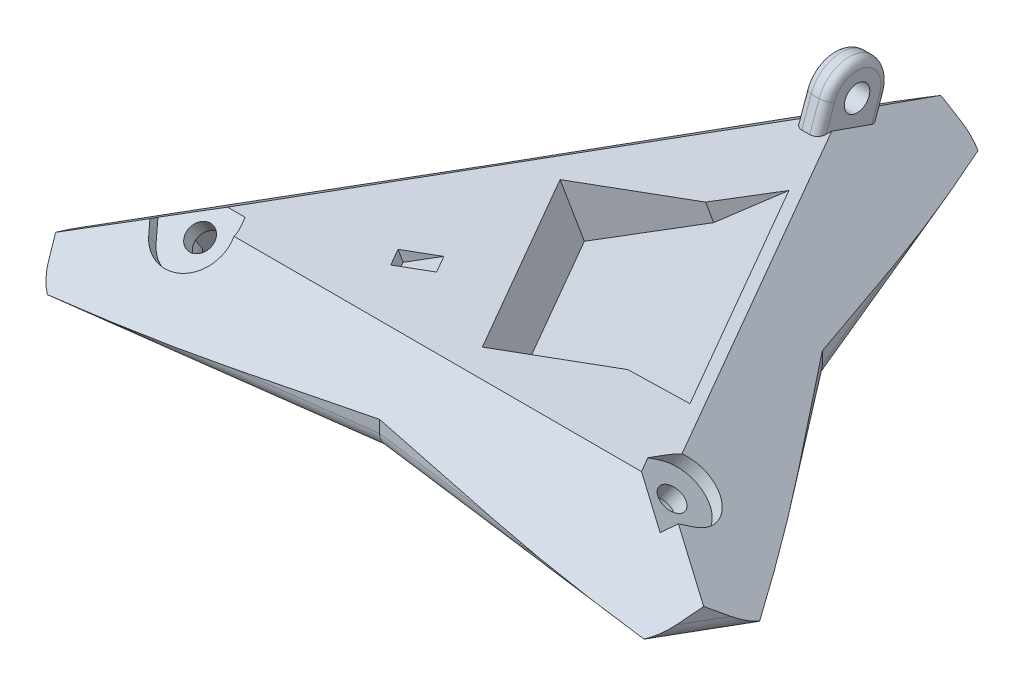
SolidWorks part; units mm, degrees
ref_plane "Front Plane" through (0, 0, 0) normal (0, 0, 1) x (1, 0, 0)
ref_plane "Top Plane" through (0, 0, 0) normal (0, 1, 0) x (1, 0, 0)
ref_plane "Right Plane" through (0, 0, 0) normal (1, 0, 0) x (0, 0, -1)
sketch "Sketch2" plane through (0, 0, 0) normal (0, 1, 0) x (1, 0, 0)
  line L0 (0, 57.735) -> (-50, -28.8675)
  line L1 (-50, -28.8675) -> (50, -28.8675)
  line L2 (50, -28.8675) -> (0, 57.735)
  line L3 (0, 0) -> (0, 57.735) construction
  line L4 (50, -28.8675) -> (0, 0) construction
  line L5 (0, 0) -> (-50, -28.8675) construction
  line L6 (0, 0) -> (0, -28.8675) construction
  line L7 (0, 0) -> (25, 14.4338) construction
  line L8 (0, 0) -> (-25, 14.4338) construction
  line L9 (10, 40.4145) -> (0, 34.641) construction
  line L10 (0, 34.641) -> (-10, 40.4145) construction
  dimension "D1" = 20
sketch "Sketch3" plane through (0, 0, 0) normal (1, 0, 0) x (0, 0, -1)
  line L0 (-28.8675, 0) -> (-19.245, 27.2166) construction
  line L1 (-19.245, 27.2166) -> (0, 20.4124) construction
  line L2 (0, 20.4124) -> (-28.8675, 0) construction
  line L3 (-19.245, 27.2166) -> (-28.983, -0.3266) construction
  line L4 (-28.983, -0.3266) -> (0.2309, 20.3308)
  line L5 (0.2309, 20.3308) -> (-19.245, 27.2166)
  line L6 (-28.983, -0.3266) -> (-28.983, 27.2166)
  line L7 (-28.983, 27.2166) -> (-19.245, 27.2166)
  line L8 (0, 0) -> (0, 103.8474) construction
  dimension "D1" = 0.2
ref_plane "Plane1" through (0, 0, 0) normal (0.5, 0, 0.866) x (0.866, 0, -0.5)
sketch "Sketch4" plane through (0, 0, 0) normal (0.5, 0, 0.866) x (0.866, 0, -0.5)
  line L0 (0, 20.4124) -> (19.245, 27.2166) construction
  line L1 (19.245, 27.2166) -> (28.8675, 0) construction
  line L2 (28.8675, 0) -> (0, 20.4124) construction
  line L3 (0, 81.6497) -> (0, 0) construction
  line L4 (-0.2309, 20.3308) -> (19.245, 27.2166)
  line L5 (19.245, 27.2166) -> (28.983, -0.3266) construction
  line L6 (28.983, -0.3266) -> (-0.2309, 20.3308)
  line L7 (19.245, 27.2166) -> (28.983, 27.2166)
  line L8 (28.983, 27.2166) -> (28.983, -0.3266)
  dimension "D1" = 0.2
ref_plane "Plane2" through (0, 0, 0) normal (0.5, 0, -0.866) x (-0.866, 0, -0.5)
sketch "Sketch5" plane through (0, 0, 0) normal (0.5, 0, -0.866) x (-0.866, 0, -0.5)
  line L0 (19.245, 27.2166) -> (0, 20.4124) construction
  line L1 (0, 20.4124) -> (28.8675, 0) construction
  line L2 (28.8675, 0) -> (19.245, 27.2166) construction
  line L3 (19.245, 27.2166) -> (-0.2309, 20.3308)
  line L4 (-0.2309, 20.3308) -> (28.983, -0.3266)
  line L5 (28.983, -0.3266) -> (19.245, 27.2166) construction
  line L6 (19.245, 27.2166) -> (28.983, 27.2166)
  line L7 (28.983, 27.2166) -> (28.983, -0.3266)
  dimension "D1" = 0.2
extrude "Boss-Extrude1" add sketch "Sketch2" along normal up to vertex (20.4124 mm away) up to point (0, 20.4124, 0)
extrude "Cut-Extrude2" cut sketch "Sketch3" against normal up to vertex (50 mm away) from vertex at 50 starting at point (50, 0, 28.8675)
extrude "Cut-Extrude3" cut sketch "Sketch4" along normal through all and the other way through all
extrude "Cut-Extrude4" cut sketch "Sketch5" along normal through all from vertex at -50 starting at point (-50, 0, 28.8675)
sketch "Sketch6" plane through (0, 0, 0) normal (0, 1, 0) x (1, 0, 0)
  line L0 (0, 0) -> (40.7397, -23.5211) construction
  line L1 (0, 0) -> (-40.7397, -23.5211) construction
  line L2 (0, 0) -> (0, -23.5211) construction
  line L3 (0, 0) -> (0, 47.0422) construction
  line L4 (0, 0) -> (-20.3699, 11.7606) construction
  line L5 (0, 0) -> (20.3699, 11.7606) construction
  line L6 (0, 0) -> (25, 14.4338) construction
  line L7 (50, -28.8675) -> (0, 0) construction
  line L8 (49.4, -28.5211) -> (0, 57.0422) construction
  line L9 (40.7397, -23.5211) -> (37.853, -28.5211) construction
  line L10 (0, 57.0422) -> (-49.4, -28.5211) construction
  line L11 (-49.4, -28.5211) -> (49.4, -28.5211) construction
  line L12 (37.853, -28.5211) -> (0, -23.5211)
  line L13 (0, -23.5211) -> (-37.853, -28.5211)
  line L14 (-37.853, -28.5211) -> (-40.7397, -23.5211) construction
  line L15 (-40.7397, -23.5211) -> (-43.6265, -18.5211) construction
  line L16 (-43.6265, -18.5211) -> (-20.3699, 11.7606)
  line L18 (5.7735, 47.0422) -> (-5.7735, 47.0422)
  line L19 (-37.853, -28.5211) -> (-43.6265, -18.5211)
  line L21 (20.3699, 11.7606) -> (43.6265, -18.5211)
  line L22 (43.6265, -18.5211) -> (40.7397, -23.5211) construction
  line L23 (0, 57.0422) -> (49.4, -28.5211) construction
  line L24 (0, 0) -> (0, 57.735) construction
  line L27 (43.6265, -18.5211) -> (37.853, -28.5211)
  line L35 (50, -28.8675) -> (0, 57.735) construction
  line L36 (50, -28.8675) -> (0, 57.735) construction
  line L37 (0, 57.735) -> (-50, -28.8675) construction
  line L38 (0, 57.735) -> (-50, -28.8675) construction
  line L46 (20.3699, 11.7606) -> (5.7735, 47.0422)
  line L47 (-5.7735, 47.0422) -> (-20.3699, 11.7606)
  circle A0 centre (0, 0) radius 47.0422 construction
  circle A1 centre (0, 0) radius 23.5211 construction
  circle A2 centre (0, 0) radius 57.0422 construction
  dimension "D1" = 10
  dimension "D2" = 5
extrude "Cut-Extrude5" cut sketch "Sketch6" along normal through all flip side to cut
sketch "Sketch7" plane through (0, 0, 0) normal (1, 0, 0) x (0, 0, -1)
  line L0 (31.2288, 11.3333) -> (27.2218, 0) construction
  line L1 (35.7071, 0) -> (27.2218, 0) construction
  line L2 (38.7712, 8.6667) -> (35.7071, 0) construction
  line L3 (31.2288, 11.3333) -> (27.2218, 0)
  line L4 (35.7071, 0) -> (27.2218, 0)
  line L5 (38.7712, 8.6667) -> (35.7071, 0)
  arc A0 (38.7712, 8.6667) -> (31.2288, 11.3333) centre (35, 10) ccw construction
  arc A1 (38.7712, 8.6667) -> (31.2288, 11.3333) centre (35, 10) ccw
  circle A2 centre (35, 10) radius 1.6 construction
  circle A3 centre (35, 10) radius 1.6 construction
  circle A4 centre (35, 10) radius 4 construction
  circle A5 centre (35, 10) radius 4 construction
sketch "Sketch8" plane through (0, 0, 0) normal (0, 1, 0) x (1, 0, 0)
  line L0 (0, 27.2218) -> (0, 35.7071) construction
  line L1 (-1.5, 27.2218) -> (1.5, 27.2218)
  line L2 (-1.5, 27.2218) -> (-1.5, 35.7071)
  line L3 (-1.5, 35.7071) -> (1.5, 35.7071)
  line L4 (1.5, 27.2218) -> (1.5, 35.7071)
  line L5 (0, 31.4645) -> (-1.5, 31.4645) construction
  line L6 (0, 31.4645) -> (1.5, 31.4645) construction
  line L7 (3.7, 27.2218) -> (3.9, 27.2218) construction
  line L8 (1.8, 27.2218) -> (3.7, 27.2218)
  line L9 (1.8, 27.2218) -> (1.8, 35.7071)
  line L10 (1.8, 35.7071) -> (3.7, 35.7071)
  line L11 (3.7, 27.2218) -> (3.7, 35.7071)
  line L12 (-1.8, 27.2218) -> (-3.7, 27.2218)
  line L13 (-1.8, 27.2218) -> (-1.8, 35.7071)
  line L14 (-1.8, 35.7071) -> (-3.7, 35.7071)
  line L15 (-3.7, 27.2218) -> (-3.7, 35.7071)
  line L16 (3.9, 27.2218) -> (3.9, 35.7071) construction
  line L17 (3.9, 35.7071) -> (3.7, 35.7071) construction
  line L18 (-3.7, 35.7071) -> (-3.9, 35.7071) construction
  line L19 (-3.9, 35.7071) -> (-3.9, 27.2218) construction
  line L20 (-3.9, 27.2218) -> (-3.7, 27.2218) construction
  line L21 (-1.8, 27.2218) -> (-1.5, 27.2218) construction
  line L22 (1.8, 27.2218) -> (1.5, 27.2218) construction
  line L23 (-1.8, 35.7071) -> (-1.5, 35.7071) construction
  line L24 (1.5, 35.7071) -> (1.8, 35.7071) construction
  dimension "D1" = 3
  dimension "D2" = 0.3
  dimension "D3" = 0.2
  dimension "D4" = 1.9
ref_plane "Plane3" through (0, 8, 0) normal (0, 1, 0) x (1, 0, 0)
sketch "Sketch10" plane through (0, 8, 0) normal (0, 1, 0) x (1, 0, 0)
  circle A0 centre (0, 0) radius 57.0422 construction
  circle A1 centre (0, 0) radius 57.0422
extrude "Cut-Extrude7" cut sketch "Sketch10" along normal through all
extrude "Boss-Extrude2" add sketch "Sketch7" along normal up to vertex (1.5 mm away) and the other way up to vertex (1.5 mm away) up to point (1.5, 0, -35.7071) other way up to point (-1.5, 0, -35.7071)
sketch "Sketch9" plane through (0, 0, 0) normal (1, 0, 0) x (0, 0, -1)
  circle A0 centre (35, 10) radius 1.6 construction
  circle A1 centre (35, 10) radius 1.6
extrude "Cut-Extrude6" cut sketch "Sketch9" against normal through all and the other way through all
fillet "Fillet1" radius 2 9 edges at (40.7397, 0, 23.5211) (18.9265, 0, 26.0211) (-18.9265, 0, 26.0211) (-40.7397, 0, 23.5211) (-31.9982, 0, 3.3803) (-13.0717, 0, -29.4014) (0, 0, -47.0422) (31.9982, 0, 3.3803) (13.0717, 0, -29.4014)
fillet "Fillet2" radius 1 6 edges at (-1.5, 7.2776, -38.2801) (-1.5, 9.6667, -30.6395) (1.5, 7.2776, -38.2801) (1.5, 9.6667, -30.6395) (-1.5, 13.7712, -36.3333) (1.5, 13.7712, -36.3333)
ref_plane "Plane7" through (3.7, 0, 0) normal (1, 0, 0) x (0, 0, -1)
sketch "Sketch15" plane through (3.7, 0, 0) normal (1, 0, 0) x (0, 0, -1)
  circle A1 centre (35, 10) radius 2.85 construction
  circle A2 centre (35, 10) radius 2.85 construction
  circle A3 centre (35, 10) radius 3.15
  dimension "D1" = 0.3
ref_plane "Plane8" through (-3.7, 0, 0) normal (1, 0, 0) x (0, 0, -1)
sketch "Sketch16" plane through (-3.7, 0, 0) normal (1, 0, 0) x (0, 0, -1)
  line L0 (33.2391, 13.05) -> (31.4782, 10)
  line L1 (31.4782, 10) -> (33.2391, 6.95)
  line L2 (33.2391, 6.95) -> (36.7609, 6.95)
  line L3 (36.7609, 6.95) -> (38.5218, 10)
  line L4 (38.5218, 10) -> (36.7609, 13.05)
  line L5 (36.7609, 13.05) -> (33.2391, 13.05)
  line L6 (38.1754, 10) -> (36.5877, 12.75)
  line L7 (36.5877, 12.75) -> (33.4123, 12.75)
  line L8 (33.4123, 12.75) -> (31.8246, 10)
  line L9 (31.8246, 10) -> (33.4123, 7.25)
  line L10 (33.4123, 7.25) -> (36.5877, 7.25)
  line L11 (36.5877, 7.25) -> (38.1754, 10)
  line L12 (38.1754, 10) -> (36.5877, 12.75) construction
  line L13 (36.5877, 12.75) -> (33.4123, 12.75) construction
  line L14 (33.4123, 12.75) -> (31.8246, 10) construction
  line L15 (31.8246, 10) -> (33.4123, 7.25) construction
  line L16 (33.4123, 7.25) -> (36.5877, 7.25) construction
  line L17 (36.5877, 7.25) -> (38.1754, 10) construction
  dimension "D1" = 0
  dimension "D2" = 0.3
sketch "Sketch17" plane through (0, 8, 0) normal (0, 1, 0) x (1, 0, 0)
  line L0 (-10, 10.75) -> (-10, 20.75) construction
  line L1 (10, 20.75) -> (-10, 20.75) construction
  line L2 (10, 10.75) -> (10, 20.75) construction
  line L3 (10, 10.75) -> (-10, 10.75) construction
  line L4 (-10, 10.75) -> (-10, 20.75)
  line L5 (10, 20.75) -> (-10, 20.75)
  line L6 (10, 10.75) -> (10, 20.75)
  line L7 (10, 10.75) -> (-10, 10.75)
  line L8 (-13.75, -9.8438) -> (-13.75, 10.1562) construction
  line L9 (-13.75, 10.1562) -> (-3.75, 10.1562) construction
  line L10 (-3.75, -9.8438) -> (-3.75, 10.1562) construction
  line L11 (-13.75, -9.8438) -> (-3.75, -9.8438) construction
  line L12 (-13.75, -9.8438) -> (-13.75, 10.1562)
  line L13 (-13.75, 10.1562) -> (-3.75, 10.1562)
  line L14 (-3.75, -9.8438) -> (-3.75, 10.1562)
  line L15 (-13.75, -9.8438) -> (-3.75, -9.8438)
  line L16 (7, -9.8438) -> (7, 10.1562) construction
  line L17 (-3, 10.1562) -> (7, 10.1562) construction
  line L18 (-3, -9.8438) -> (-3, 10.1562) construction
  line L19 (-3, -9.8438) -> (7, -9.8438) construction
  line L20 (7, -9.8438) -> (7, 10.1562)
  line L21 (-3, 10.1562) -> (7, 10.1562)
  line L22 (-3, -9.8438) -> (-3, 10.1562)
  line L23 (-3, -9.8438) -> (7, -9.8438)
  line L25 (12.75, 10.1562) -> (7.75, 10.1562)
  line L26 (12.75, 10.1562) -> (12.75, -9.8438)
  line L27 (12.75, -9.8438) -> (7.75, -9.8438)
  line L28 (7.75, 10.1562) -> (7.75, -9.8438)
  line L29 (10, -10.25) -> (-10, -10.25)
  line L30 (10, -10.25) -> (10, -15.25)
  line L31 (10, -15.25) -> (-10, -15.25)
  line L32 (-10, -10.25) -> (-10, -15.25)
sketch "Sketch18" plane through (0, 27.2166, 19.245) normal (0.5, 0.8165, -0.2887) x (0.866, -0.4714, 0.1667)
  line L0 (35.9192, -0.3) -> (39.0541, 8.5667)
  line L1 (30.9459, 11.4333) -> (26.7976, -0.3)
  line L2 (26.7976, -0.3) -> (35.9192, -0.3)
  line L3 (31.2288, 11.3333) -> (27.2218, 0)
  line L4 (27.2218, 0) -> (35.7071, 0)
  line L5 (35.7071, 0) -> (38.7712, 8.6667)
  line L6 (31.2288, 11.3333) -> (27.2218, 0) construction
  line L7 (27.2218, 0) -> (35.7071, 0) construction
  line L8 (35.7071, 0) -> (38.7712, 8.6667) construction
  arc A0 (39.0541, 8.5667) -> (30.9459, 11.4333) centre (35, 10) ccw
  arc A1 (38.7712, 8.6667) -> (31.2288, 11.3333) centre (35, 10) ccw
  arc A2 (38.7712, 8.6667) -> (31.2288, 11.3333) centre (35, 10) ccw construction
  dimension "D1" = 0
  dimension "D2" = 0.3
extrude "Cut-Extrude8" cut sketch "Sketch18" against normal up to vertex (1.8 mm away)
sketch "Sketch19" plane through (0, 27.2166, 19.245) normal (0.5, 0.8165, -0.2887) x (0.866, -0.4714, 0.1667)
  circle A0 centre (35, 10) radius 1.6 construction
  circle A1 centre (35, 10) radius 1.6
extrude "Cut-Extrude9" cut sketch "Sketch19" against normal through all
sketch "Sketch20" plane through (-1.85, 24.1955, 20.3131) normal (0.5, 0.8165, -0.2887) x (0.866, -0.4714, 0.1667)
  circle A1 centre (35, 10) radius 3.15
  circle A2 centre (35, 10) radius 3.15
  dimension "D1" = 0
extrude "Cut-Extrude10" cut sketch "Sketch20" against normal through all
sketch "Sketch22" plane through (-16.6667, 27.2166, -9.6225) normal (0, 0.8165, 0.5774) x (-0.5774, -0.4714, 0.6667)
  line L0 (26.7976, -0.3) -> (35.9192, -0.3)
  line L1 (35.9192, -0.3) -> (39.0541, 8.5667)
  line L2 (30.9459, 11.4333) -> (26.7976, -0.3)
  line L3 (31.2288, 11.3333) -> (27.2218, 0)
  line L4 (27.2218, 0) -> (35.7071, 0)
  line L5 (35.7071, 0) -> (38.7712, 8.6667)
  line L6 (31.2288, 11.3333) -> (27.2218, 0) construction
  line L7 (27.2218, 0) -> (35.7071, 0) construction
  line L8 (35.7071, 0) -> (38.7712, 8.6667) construction
  arc A0 (39.0541, 8.5667) -> (30.9459, 11.4333) centre (35, 10) ccw
  arc A1 (38.7712, 8.6667) -> (31.2288, 11.3333) centre (35, 10) ccw
  arc A2 (38.7712, 8.6667) -> (31.2288, 11.3333) centre (35, 10) ccw construction
  dimension "D1" = 0
  dimension "D2" = 0.3
extrude "Cut-Extrude11" cut sketch "Sketch22" against normal up to vertex (1.8 mm away)
sketch "Sketch23" plane through (-16.6667, 27.2166, -9.6225) normal (0, 0.8165, 0.5774) x (-0.5774, -0.4714, 0.6667)
  circle A0 centre (35, 10) radius 1.6 construction
  circle A1 centre (35, 10) radius 1.6
extrude "Cut-Extrude12" cut sketch "Sketch23" against normal through all
sketch "Sketch24" plane through (-16.6667, 24.1955, -11.7587) normal (0, 0.8165, 0.5774) x (-0.5774, -0.4714, 0.6667)
  line L6 (33.2391, 13.05) -> (31.4782, 10)
  line L7 (31.4782, 10) -> (33.2391, 6.95)
  line L8 (33.2391, 6.95) -> (36.7609, 6.95)
  line L9 (36.7609, 6.95) -> (38.5218, 10)
  line L10 (38.5218, 10) -> (36.7609, 13.05)
  line L11 (36.7609, 13.05) -> (33.2391, 13.05)
  line L12 (33.2391, 13.05) -> (31.4782, 10)
  line L13 (31.4782, 10) -> (33.2391, 6.95)
  line L14 (33.2391, 6.95) -> (36.7609, 6.95)
  line L15 (36.7609, 6.95) -> (38.5218, 10)
  line L16 (38.5218, 10) -> (36.7609, 13.05)
  line L17 (36.7609, 13.05) -> (33.2391, 13.05)
  dimension "D1" = 0
extrude "Cut-Extrude13" cut sketch "Sketch24" against normal through all
ref_plane "Plane9" through (-0.6481, 2.1166, 0.3742) normal (0.2887, -0.9428, -0.1667) x (-0.9574, -0.2843, -0.0503)
sketch "Sketch25" plane through (-0.6481, 2.1166, 0.3742) normal (0.2887, -0.9428, -0.1667) x (-0.9574, -0.2843, -0.0503)
  line L0 (-49.322, -28.4268) -> (2.9013, 56.8535) construction
  line L1 (-49.322, -28.4268) -> (2.9013, 56.8535) construction
  line L2 (1.3661, 9.8262) -> (-11.4514, 33.4157)
  line L3 (-11.4514, 33.4157) -> (-34.9693, -4.9889)
  line L4 (-34.9693, -4.9889) -> (-8.1315, -5.6833)
  line L5 (-7.8599, 4.8132) -> (-23.2104, 14.2134) construction
  arc A0 (-8.1315, -5.6833) -> (1.3661, 9.8262) centre (-7.8599, 4.8132) ccw
  circle A1 centre (-7.8599, 4.8132) radius 10
  circle A2 centre (-7.8599, 4.8132) radius 10 construction
  circle A5 centre (-7.8599, 4.8132) radius 10.5 construction
  point P9 (2.6401, 4.8132)
  dimension "D3" = 60
  dimension "D1" = 0
  dimension "D2" = 0.5
extrude "Cut-Extrude14" cut sketch "Sketch25" against normal through all
ref_plane "Plane10" through (-1.2254, 4.0022, 0.7075) normal (0.2887, -0.9428, -0.1667) x (-0.9574, -0.2843, -0.0503)
sketch "Sketch26" plane through (-1.2254, 4.0022, 0.7075) normal (0.2887, -0.9428, -0.1667) x (-0.9574, -0.2843, -0.0503)
  line L0 (-21.596, 2.4882) -> (-23.7861, -1.0883) construction
  line L1 (-23.7861, -1.0883) -> (-5.8773, -12.0552)
  line L2 (-5.8773, -12.0552) -> (8.0663, 10.7147)
  line L3 (8.0663, 10.7147) -> (-9.8425, 21.6816)
  line L4 (-9.8425, 21.6816) -> (-12.0327, 18.1051) construction
  line L5 (-9.8425, 21.6816) -> (-23.7861, -1.0883)
  line L38 (-11.6063, 17.8439) -> (-16.8873, 20.7092)
  line L39 (-9.6772, 20.994) -> (-11.6063, 17.8439)
  line L40 (7.3788, 10.5494) -> (-9.6772, 20.994)
  line L41 (-6.0426, -11.3677) -> (7.3788, 10.5494)
  line L42 (-23.0986, -0.923) -> (-6.0426, -11.3677)
  line L43 (-21.1696, 2.2271) -> (-23.0986, -0.923)
  line L44 (-26.1222, 5.6286) -> (-21.1696, 2.2271)
  line L45 (-25.5041, 6.6379) -> (-26.1222, 5.6286)
  line L46 (-22.8291, 5.1866) -> (-25.5041, 6.6379)
  line L47 (-22.1019, 5.1931) -> (-22.8291, 5.1866)
  line L48 (-21.7221, 5.8133) -> (-22.1019, 5.1931)
  line L49 (-22.0468, 6.464) -> (-21.7221, 5.8133)
  line L50 (-24.5555, 8.1871) -> (-22.0468, 6.464)
  line L51 (-23.9374, 9.1963) -> (-24.5555, 8.1871)
  line L52 (-21.2624, 7.745) -> (-23.9374, 9.1963)
  line L53 (-20.5352, 7.7516) -> (-21.2624, 7.745)
  line L54 (-20.1554, 8.3717) -> (-20.5352, 7.7516)
  line L55 (-20.4801, 9.0224) -> (-20.1554, 8.3717)
  line L56 (-22.9888, 10.7455) -> (-20.4801, 9.0224)
  line L57 (-22.3707, 11.7548) -> (-22.9888, 10.7455)
  line L58 (-19.6957, 10.3034) -> (-22.3707, 11.7548)
  line L59 (-18.9685, 10.31) -> (-19.6957, 10.3034)
  line L60 (-18.5887, 10.9301) -> (-18.9685, 10.31)
  line L61 (-18.9134, 11.5808) -> (-18.5887, 10.9301)
  line L62 (-21.4221, 13.3039) -> (-18.9134, 11.5808)
  line L63 (-20.804, 14.3132) -> (-21.4221, 13.3039)
  line L64 (-18.129, 12.8618) -> (-20.804, 14.3132)
  line L65 (-17.4018, 12.8684) -> (-18.129, 12.8618)
  line L66 (-17.022, 13.4885) -> (-17.4018, 12.8684)
  line L67 (-17.3467, 14.1392) -> (-17.022, 13.4885)
  line L68 (-19.8554, 15.8623) -> (-17.3467, 14.1392)
  line L69 (-19.2373, 16.8716) -> (-19.8554, 15.8623)
  line L70 (-16.5623, 15.4202) -> (-19.2373, 16.8716)
  line L71 (-15.8351, 15.4268) -> (-16.5623, 15.4202)
  line L72 (-14.672, 17.3262) -> (-15.8351, 15.4268)
  line L73 (-14.9967, 17.9769) -> (-14.672, 17.3262)
  line L74 (-17.5054, 19.6999) -> (-14.9967, 17.9769)
  line L75 (-16.8873, 20.7092) -> (-17.5054, 19.6999)
  line L76 (-11.6063, 17.8439) -> (-16.8873, 20.7092) construction
  line L77 (-9.6772, 20.994) -> (-11.6063, 17.8439) construction
  line L78 (7.3788, 10.5494) -> (-9.6772, 20.994) construction
  line L79 (-6.0426, -11.3677) -> (7.3788, 10.5494) construction
  line L80 (-23.0986, -0.923) -> (-6.0426, -11.3677) construction
  line L81 (-21.1696, 2.2271) -> (-23.0986, -0.923) construction
  line L82 (-26.1222, 5.6286) -> (-21.1696, 2.2271) construction
  line L83 (-25.5041, 6.6379) -> (-26.1222, 5.6286) construction
  line L84 (-22.8291, 5.1866) -> (-25.5041, 6.6379) construction
  line L85 (-22.1019, 5.1931) -> (-22.8291, 5.1866) construction
  line L86 (-21.7221, 5.8133) -> (-22.1019, 5.1931) construction
  line L87 (-22.0468, 6.464) -> (-21.7221, 5.8133) construction
  line L88 (-24.5555, 8.1871) -> (-22.0468, 6.464) construction
  line L89 (-23.9374, 9.1963) -> (-24.5555, 8.1871) construction
  line L90 (-21.2624, 7.745) -> (-23.9374, 9.1963) construction
  line L91 (-20.5352, 7.7516) -> (-21.2624, 7.745) construction
  line L92 (-20.1554, 8.3717) -> (-20.5352, 7.7516) construction
  line L93 (-20.4801, 9.0224) -> (-20.1554, 8.3717) construction
  line L94 (-22.9888, 10.7455) -> (-20.4801, 9.0224) construction
  line L95 (-22.3707, 11.7548) -> (-22.9888, 10.7455) construction
  line L96 (-19.6957, 10.3034) -> (-22.3707, 11.7548) construction
  line L97 (-18.9685, 10.31) -> (-19.6957, 10.3034) construction
  line L98 (-18.5887, 10.9301) -> (-18.9685, 10.31) construction
  line L99 (-18.9134, 11.5808) -> (-18.5887, 10.9301) construction
  line L100 (-21.4221, 13.3039) -> (-18.9134, 11.5808) construction
  line L101 (-20.804, 14.3132) -> (-21.4221, 13.3039) construction
  line L102 (-18.129, 12.8618) -> (-20.804, 14.3132) construction
  line L103 (-17.4018, 12.8684) -> (-18.129, 12.8618) construction
  line L104 (-17.022, 13.4885) -> (-17.4018, 12.8684) construction
  line L105 (-17.3467, 14.1392) -> (-17.022, 13.4885) construction
  line L106 (-19.8554, 15.8623) -> (-17.3467, 14.1392) construction
  line L107 (-19.2373, 16.8716) -> (-19.8554, 15.8623) construction
  line L108 (-16.5623, 15.4202) -> (-19.2373, 16.8716) construction
  line L109 (-15.8351, 15.4268) -> (-16.5623, 15.4202) construction
  line L110 (-14.672, 17.3262) -> (-15.8351, 15.4268) construction
  line L111 (-14.9967, 17.9769) -> (-14.672, 17.3262) construction
  line L112 (-17.5054, 19.6999) -> (-14.9967, 17.9769) construction
  line L113 (-16.8873, 20.7092) -> (-17.5054, 19.6999) construction
  dimension "D1" = 0
  dimension "D2" = 0.5
extrude "Cut-Extrude15" cut sketch "Sketch26" against normal through all and the other way up to surface other way up to face at (7.1053, 5.2819, -4.1022)
ref_plane "Plane11" through (17.7181, 19.0074, -9.3635) normal (0.5, 0, 0.866) x (-0.2887, 0.9428, 0.1667)
sketch "Sketch27" plane through (17.7181, 19.0074, -9.3635) normal (0.5, 0, 0.866) x (-0.2887, 0.9428, 0.1667)
  line L0 (0, 6) -> (18.3124, 6)
  line L36 (17.9979, 0) -> (18.3124, 6)
  line L37 (18.3124, 6) -> (18.3124, 37)
  line L38 (18.3124, 37) -> (0, 37)
  line L39 (0, 37) -> (0, 6)
  line L40 (0, 6) -> (0.3144, 0)
  line L41 (0.3144, 0) -> (1.4979, 0)
  line L42 (1.4979, 0) -> (1.6572, 3.0393)
  line L43 (1.6572, 3.0393) -> (2.0426, 3.656)
  line L44 (2.0426, 3.656) -> (2.7698, 3.656)
  line L45 (2.7698, 3.656) -> (3.1552, 3.0393)
  line L46 (3.1552, 3.0393) -> (3.3144, 0)
  line L47 (3.3144, 0) -> (4.4979, 0)
  line L48 (4.4979, 0) -> (4.6572, 3.0393)
  line L49 (4.6572, 3.0393) -> (5.0426, 3.656)
  line L50 (5.0426, 3.656) -> (5.7698, 3.656)
  line L51 (5.7698, 3.656) -> (6.1552, 3.0393)
  line L52 (6.1552, 3.0393) -> (6.3144, 0)
  line L53 (6.3144, 0) -> (7.4979, 0)
  line L54 (7.4979, 0) -> (7.6572, 3.0393)
  line L55 (7.6572, 3.0393) -> (8.0426, 3.656)
  line L56 (8.0426, 3.656) -> (8.7698, 3.656)
  line L57 (8.7698, 3.656) -> (9.1552, 3.0393)
  line L58 (9.1552, 3.0393) -> (9.3144, 0)
  line L59 (9.3144, 0) -> (10.4979, 0)
  line L60 (10.4979, 0) -> (10.6572, 3.0393)
  line L61 (10.6572, 3.0393) -> (11.0426, 3.656)
  line L62 (11.0426, 3.656) -> (11.7698, 3.656)
  line L63 (11.7698, 3.656) -> (12.1552, 3.0393)
  line L64 (12.1552, 3.0393) -> (12.3144, 0)
  line L65 (12.3144, 0) -> (13.4979, 0)
  line L66 (13.4979, 0) -> (13.6572, 3.0393)
  line L67 (13.6572, 3.0393) -> (14.0426, 3.656)
  line L68 (14.0426, 3.656) -> (16.2698, 3.656)
  line L69 (16.2698, 3.656) -> (16.6552, 3.0393)
  line L70 (16.6552, 3.0393) -> (16.8144, 0)
  line L71 (16.8144, 0) -> (17.9979, 0)
  line L73 (18.3124, 6) -> (18.3124, 37)
  line L74 (18.3124, 37) -> (0, 37)
  line L75 (0, 37) -> (0, 6)
  dimension "D1" = 0
extrude "Cut-Extrude16" cut sketch "Sketch27" along normal blind 2.5
fillet "Fillet3" radius 1 7 edges at (-25.9388, 0, 11.6405) (-28.4291, 0, 9.4838) (-31.1993, 0, 11.0469) (-31.4791, 0, 14.7666) (-28.9888, 0, 16.9233) (-26.2186, 0, 15.3602) (29.1302, 0, 16.3319)
